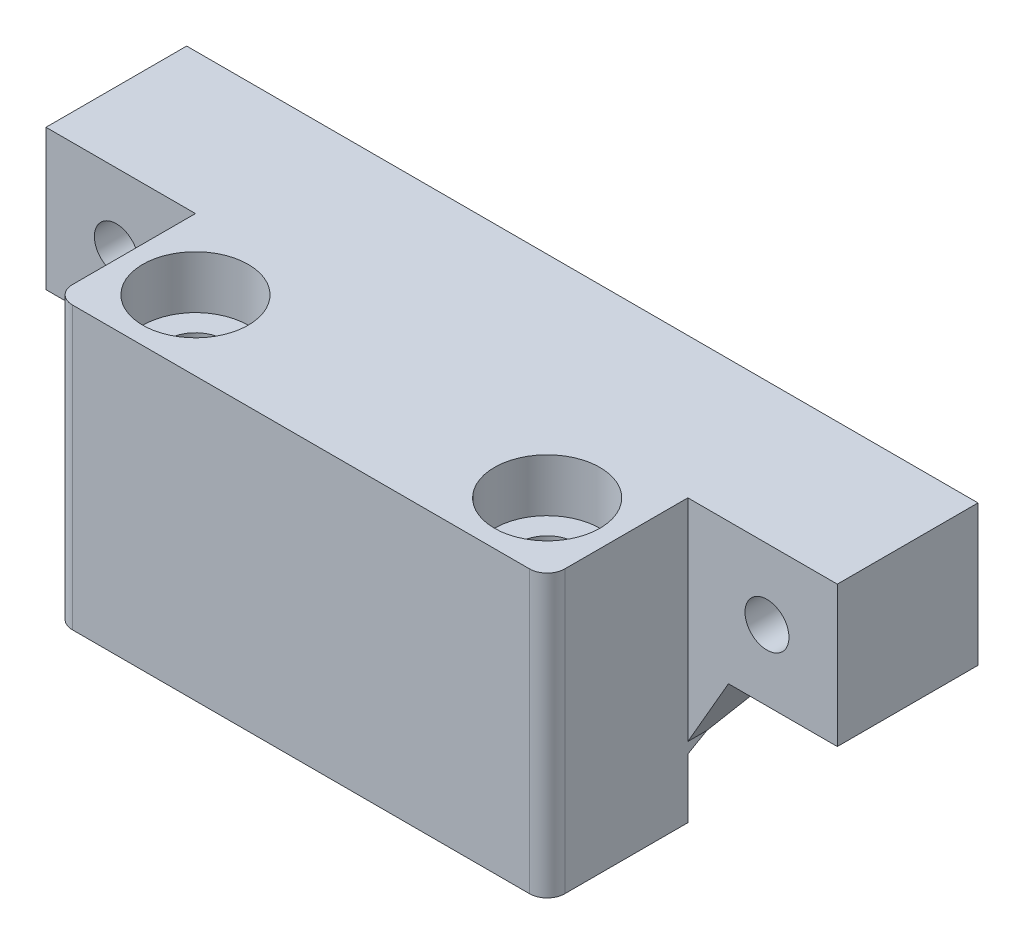
SolidWorks part; units mm, degrees
ref_plane "正面" through (0, 0, 0) normal (0, 0, 1) x (1, 0, 0)
ref_plane "平面" through (0, 0, 0) normal (0, 1, 0) x (1, 0, 0)
ref_plane "右側面" through (0, 0, 0) normal (1, 0, 0) x (0, 0, -1)
sketch "ｽｹｯﾁ1" plane through (0, 0, 0) normal (0, 0, 1) x (1, 0, 0)
  line L0 (0, 0) -> (-18.5, 0) construction
  line L1 (0, 4) -> (0, 0) construction
  line L3 (-22.5, 4) -> (22.5, 4)
  line L4 (-22.5, 4) -> (-22.5, -4)
  line L5 (-22.5, -4) -> (22.5, -4)
  line L6 (22.5, 4) -> (22.5, -4)
  line L7 (-22.5, 4) -> (22.5, -4) construction
  line L8 (-22.5, -4) -> (22.5, 4) construction
  circle A0 centre (-18.5, 0) radius 1.25
  circle A1 centre (18.5, 0) radius 1.25
  dimension "D1" = 2.5
  dimension "D2" = 18.5
  dimension "D3" = 45
  dimension "D4" = 8
extrude "ﾎﾞｽ - 押し出し1" add sketch "ｽｹｯﾁ1" along normal blind 8
sketch "ｽｹｯﾁ2" plane through (0, -4, 0) normal (0, -1, 0) x (1, 0, 0)
  line L0 (-22.5, 8) -> (22.5, 8) construction
  line L1 (-14, 16) -> (14, 16)
  line L2 (-14, 16) -> (-14, 8)
  line L3 (-14, 8) -> (14, 8)
  line L4 (14, 16) -> (14, 8)
  line L5 (-14, 16) -> (14, 8) construction
  line L6 (-14, 8) -> (14, 16) construction
  line L7 (-10, 12) -> (10, 12) construction
  line L8 (0, 12) -> (0, 0) construction
  circle A0 centre (-10, 12) radius 1.6
  circle A1 centre (10, 12) radius 1.6
  point P0 (0, 12)
  point P9 (0, 12)
  dimension "D1" = 20
  dimension "D2" = 3.2
  dimension "D3" = 28
  dimension "D4" = 8
extrude "ﾎﾞｽ - 押し出し2" add sketch "ｽｹｯﾁ2" along normal blind 8 and the other way blind 8
sketch "ｽｹｯﾁ4" plane through (0, 4, 0) normal (0, 1, 0) x (1, 0, 0)
  line L0 (0, 0) -> (0, -16) construction
  line L1 (22.5, 0) -> (-22.5, 0) construction
  line L2 (14, -16) -> (-14, -16) construction
  circle A0 centre (10, -12) radius 3
  circle A1 centre (-10, -12) radius 3
  dimension "D1" = 6
extrude "ｶｯﾄ - 押し出し2" cut sketch "ｽｹｯﾁ4" against normal blind 3
fillet "ﾌｨﾚｯﾄ1" radius 1 2 edges at (-14, -4, 16) (14, -4, 16)
chamfer "面取り1" distance 8 angle 30 1 edges at (0, -4, 8) first distance on face at (0, -4, 5.3333)
chamfer "面取り2" distance 4 angle 30 2 edges at (14, -4, 4) (-14, -4, 4) first distance on face at (14, -4.6598, 8.8571) first distance on face at (-14, -4.6598, 8.8571)
sketch "ｽｹｯﾁ5" plane through (0, 0, 0) normal (0, 0, -1) x (-1, 0, 0)
  circle A0 centre (-18.5, 0) radius 2.1
  circle A1 centre (18.5, 0) radius 2.1
  dimension "D1" = 4.2
extrude "ｶｯﾄ - 押し出し3" cut sketch "ｽｹｯﾁ5" against normal blind 5
